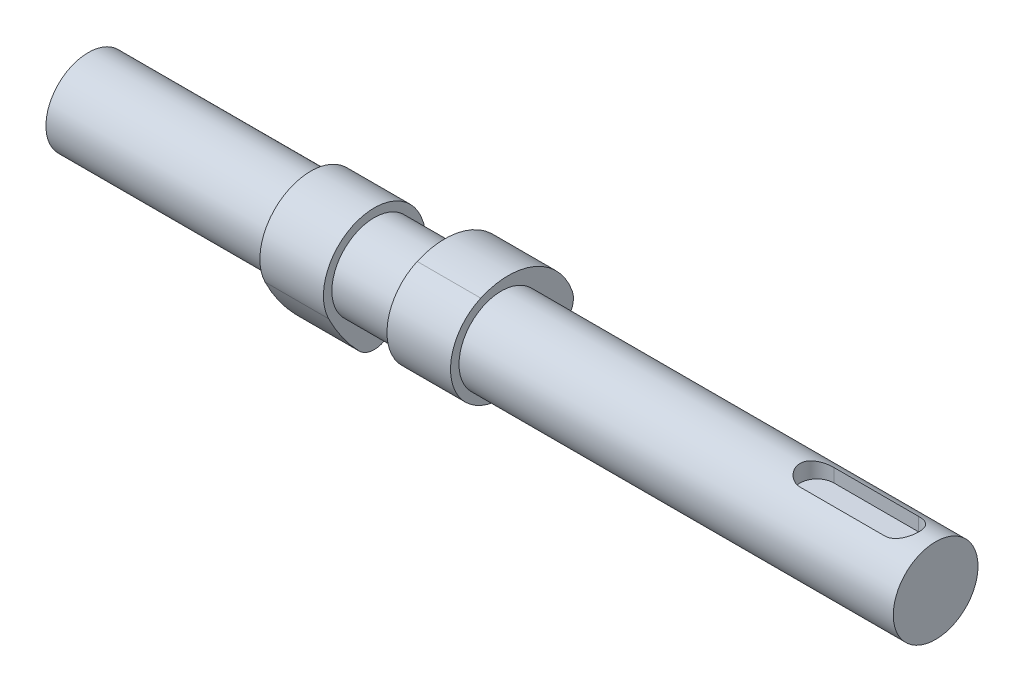
SolidWorks part; units mm, degrees
material "Ductile Iron"
ref_plane "Front Plane" through (0, 0, 0) normal (0, 0, 1) x (1, 0, 0)
ref_plane "Top Plane" through (0, 0, 0) normal (0, 1, 0) x (1, 0, 0)
ref_plane "Right Plane" through (0, 0, 0) normal (1, 0, 0) x (0, 0, -1)
sketch "Sketch1" plane through (0, 0, 0) normal (1, 0, 0) x (0, 0, -1)
  circle A0 centre (0, 0) radius 10
  dimension "D1" = 20
extrude "Boss-Extrude1" add sketch "Sketch1" against normal blind 75 and the other way blind 125
sketch "Sketch2" plane through (0, 0, 0) normal (1, 0, 0) x (0, 0, -1)
  line L0 (0, 0) -> (11.997, 0) construction
  arc A0 (-4.8671, 10.9687) -> (5.3062, -10.7631) centre (0, 0) ccw
  arc A1 (15.4795, -3.5877) -> (16.7127, 1.6619) centre (11.997, 0) ccw
  arc A2 (-4.8671, 10.9687) -> (16.7127, 1.6619) centre (1.6224, -3.6562) cw
  arc A3 (5.3062, -10.7631) -> (15.4795, -3.5877) centre (-12.3812, 25.1139) ccw
  dimension "D1" = 24
  dimension "D2" = 10
  dimension "D3" = 16
  dimension "D4" = 40
  dimension "D5" = 12.5
extrude "Boss-Extrude2" add sketch "Sketch2" along normal mid plane 15 from offset 15 separate body
mirror "Mirror1" about plane through (0, 0, 0) normal (1, 0, 0) of bodies 102
move or copy body "Body-Move/Copy1" bodies to move or copy 103 copy no rotation origin (0, 0, 0) rotation axis (-1, 0, 0) rotation angle 90
ref_plane "Plane1" through (0, 10, 0) normal (0, 1, 0) x (1, 0, 0)
sketch "Sketch3" plane through (0, 10, 0) normal (0, 1, 0) x (1, 0, 0)
  line L0 (125, 0) -> (22.5, 0) construction
  line L1 (125, -10) -> (125, 10) construction
  line L2 (22.5, -4.8671) -> (22.5, 16.7127) construction
  line L3 (97, 0) -> (117, 0) construction
  line L4 (97, 4) -> (117, 4)
  line L5 (97, -4) -> (117, -4)
  arc A0 (97, 4) -> (97, -4) centre (97, 0) ccw
  arc A1 (117, -4) -> (117, 4) centre (117, 0) ccw
  point P9 (107, 0)
  dimension "D3" = 4
  dimension "D1" = 20
  dimension "D2" = 8
extrude "Cut-Extrude1" cut sketch "Sketch3" against normal blind 4
combine bodies "Combine1" operation type add bodies to combine 105 104 102
